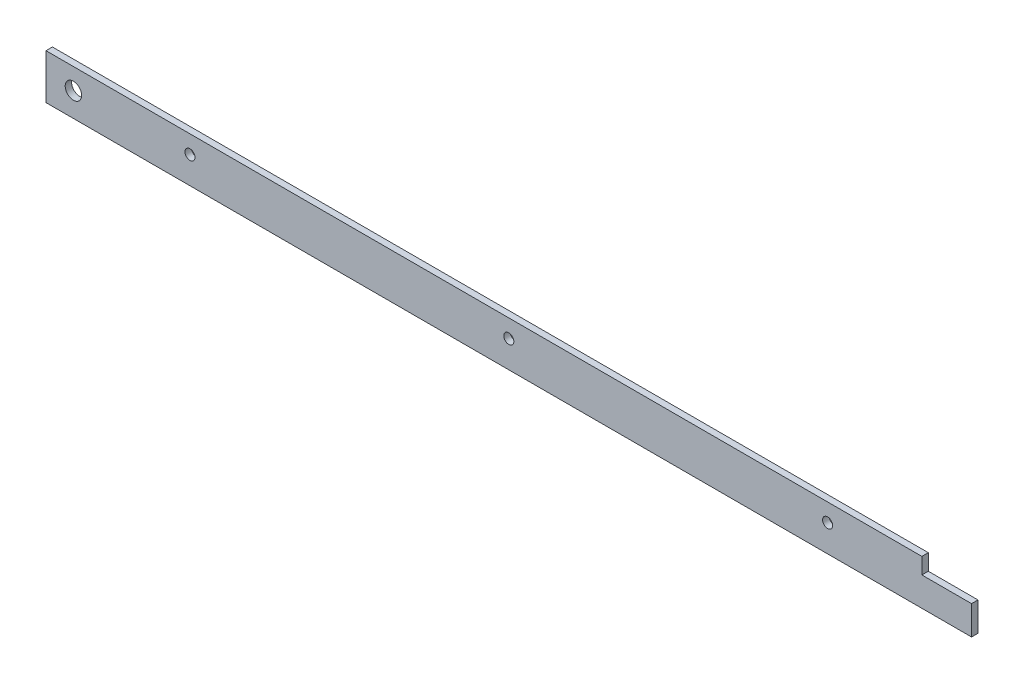
SolidWorks part; units mm, degrees
ref_plane "Front Plane" through (0, 0, 0) normal (0, 0, 1) x (1, 0, 0)
ref_plane "Top Plane" through (0, 0, 0) normal (0, 1, 0) x (1, 0, 0)
ref_plane "Right Plane" through (0, 0, 0) normal (1, 0, 0) x (0, 0, -1)
sketch "Sketch1" plane through (0, 0, 0) normal (0, 0, 1) x (1, 0, 0)
  line L6 (419.96, 17.392) -> (0, 17.392) construction
  line L9 (0, -4.833) -> (457.2, -4.833)
  line L10 (457.2, 9.447) -> (457.2, -4.833)
  line L12 (419.96, 17.392) -> (0, 17.392)
  line L13 (0, -4.833) -> (0, 17.392)
  line L14 (419.96, 17.392) -> (432.66, 17.392)
  line L15 (432.66, 9.447) -> (432.66, 17.392)
  line L16 (432.66, 24.067) -> (432.66, 17.067) construction
  line L17 (432.66, 9.447) -> (457.2, 9.447)
  line L18 (0, 20.567) -> (457.2, 20.567) construction
  line L19 (0, 20.567) -> (457.2, 20.567) construction
  circle A0 centre (13.54, 34.107) radius 13.54 construction
  circle A1 centre (13.54, 34.107) radius 13.54 construction
  circle A2 centre (13.54, 34.107) radius 4.0635 construction
  circle A3 centre (71.12, 8.5095) radius 2.4892 construction
  circle A4 centre (228.6, 8.5095) radius 2.4892 construction
  circle A5 centre (386.08, 8.5095) radius 2.4892 construction
  circle A6 centre (71.12, 8.5095) radius 2.4892
  circle A7 centre (228.6, 8.5095) radius 2.4892
  circle A8 centre (386.08, 8.5095) radius 2.4892
  circle A9 centre (13.54, 7.027) radius 4.0635
  point P31 (457.2, 9.447)
  dimension "D1" = 8.127
extrude "Boss-Extrude1" add sketch "Sketch1" along normal blind 3.175 contours L17 L15 L14 L12 L13 L9 L10 A8 A7 A6 region at (225.4525, 6.1211, 0)
